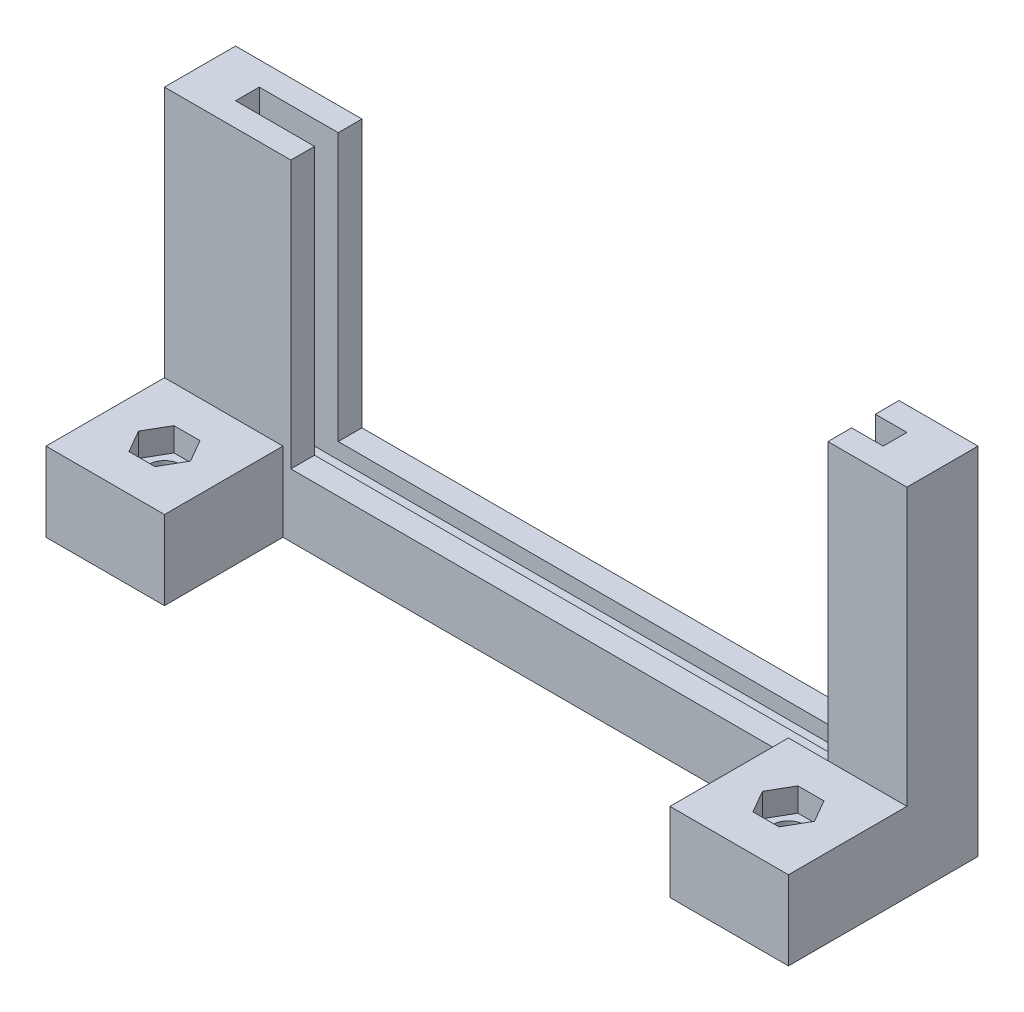
SolidWorks part; units mm, degrees
ref_plane "Plan de face" through (0, 0, 0) normal (0, 0, 1) x (1, 0, 0)
ref_plane "Plan de dessus" through (0, 0, 0) normal (0, 1, 0) x (1, 0, 0)
ref_plane "Plan de droite" through (0, 0, 0) normal (1, 0, 0) x (0, 0, -1)
sketch "Esquisse1" plane through (0, 0, 0) normal (0, 0, 1) x (1, 0, 0)
  line L17 (26.3064, -26.8419) -> (-41.6936, -26.8419)
  line L18 (26.3064, -26.8419) -> (26.3064, -34.8419) construction
  line L19 (26.3064, -34.8419) -> (-41.6936, -34.8419)
  line L20 (-41.6936, -26.8419) -> (-41.6936, -34.8419) construction
  line L21 (26.3064, 10.1581) -> (36.3064, 10.1581)
  line L22 (26.3064, 10.1581) -> (26.3064, -34.8419) construction
  line L23 (26.3064, -34.8419) -> (36.3064, -34.8419)
  line L24 (36.3064, 10.1581) -> (36.3064, -34.8419)
  line L26 (-41.6936, 7.0239) -> (-41.6936, -26.8419)
  line L27 (-41.6936, -34.8419) -> (-57.6936, -34.8419)
  line L28 (-41.6936, -34.8419) -> (-41.6936, 7.0239) construction
  line L29 (-41.6936, 7.0239) -> (-57.6936, 7.0239)
  line L30 (-57.6936, -34.8419) -> (-57.6936, 7.0239)
  line L31 (26.3064, 10.1581) -> (26.3064, -26.8419)
  dimension "D1" = 45
  dimension "D2" = 78
  dimension "D3" = 10
  dimension "D4" = 8
  dimension "D5" = 16
extrude "Boss.-Extru.1" add sketch "Esquisse1" along normal blind 3
sketch "Esquisse2" plane through (0, 0, 3) normal (0, 0, 1) x (1, 0, 0)
  line L0 (-57.6936, 7.0239) -> (-57.6936, -34.8419)
  line L1 (-57.6936, -34.8419) -> (36.3064, -34.8419)
  line L2 (36.3064, -34.8419) -> (36.3064, 10.1581)
  line L3 (36.3064, 10.1581) -> (30.3064, 10.1581)
  line L4 (36.3064, 10.1581) -> (26.3064, 10.1581) construction
  line L5 (30.3064, 10.1581) -> (30.3064, -28.8419)
  line L6 (30.3064, -28.8419) -> (-51.6936, -28.8419)
  line L7 (-51.6936, -28.8419) -> (-51.6936, 7.0239)
  line L8 (-41.6936, 7.0239) -> (-57.6936, 7.0239) construction
  line L9 (-51.6936, 7.0239) -> (-57.6936, 7.0239)
  dimension "D1" = 6
  dimension "D2" = 6
  dimension "D3" = 6
extrude "Boss.-Extru.2" add sketch "Esquisse2" along normal blind 1.5
ref_plane "Plan1" through (0, 0, 4.5) normal (0, 0, 1) x (1, 0, 0)
mirror "Symétrie3" about plane through (0, 0, 4.5) normal (0, 0, 1) of bodies 105
sketch "Esquisse3" plane through (0, -34.8419, 0) normal (0, -1, 0) x (1, 0, 0)
  line L1 (-57.6936, 9) -> (-42.6936, 9)
  line L2 (-57.6936, 9) -> (-57.6936, 24)
  line L3 (-57.6936, 24) -> (-42.6936, 24)
  line L4 (-42.6936, 9) -> (-42.6936, 24)
  line L5 (36.3064, 9) -> (21.3064, 9)
  line L6 (36.3064, 9) -> (36.3064, 24)
  line L7 (36.3064, 24) -> (21.3064, 24)
  line L8 (21.3064, 9) -> (21.3064, 24)
  dimension "D1" = 15
  dimension "D2" = 15
  dimension "D3" = 15
  dimension "D4" = 15
extrude "Boss.-Extru.3" add sketch "Esquisse3" against normal blind 10
sketch "Esquisse4" plane through (0, -24.8419, 0) normal (0, 1, 0) x (1, 0, 0)
  line L0 (-57.6936, -9) -> (-42.6936, -24) construction
  line L1 (36.3064, -9) -> (21.3064, -24) construction
  circle A0 centre (-50.1936, -16.5) radius 2
  circle A1 centre (28.8064, -16.5) radius 2
  dimension "D1" = 4
extrude "Enlèv. mat.-Extru.1" cut sketch "Esquisse4" against normal blind 10
sketch "Esquisse5" plane through (0, -24.8419, 0) normal (0, 1, 0) x (1, 0, 0)
  line L0 (-51.839, -13.65) -> (-48.5481, -13.65)
  line L1 (-48.5481, -13.65) -> (-46.9027, -16.5)
  line L3 (-48.5481, -19.35) -> (-51.839, -19.35)
  line L4 (-51.839, -19.35) -> (-53.4845, -16.5)
  line L5 (-53.4845, -16.5) -> (-51.839, -13.65)
  line L6 (-46.9027, -16.5) -> (-48.5481, -19.35)
  line L7 (-53.4845, -16.5) -> (-46.9027, -16.5) construction
  line L8 (27.161, -13.65) -> (30.4519, -13.65)
  line L9 (30.4519, -13.65) -> (32.0973, -16.5)
  line L10 (30.4519, -19.35) -> (27.161, -19.35)
  line L11 (27.161, -19.35) -> (25.5155, -16.5)
  line L12 (25.5155, -16.5) -> (27.161, -13.65)
  line L13 (32.0973, -16.5) -> (30.4519, -19.35)
  line L14 (25.5155, -16.5) -> (32.0973, -16.5) construction
  point P2 (-50.1936, -16.5)
  point P7 (-50.1936, -16.5)
  point P8 (28.8064, -16.5)
  point P11 (28.8064, -16.5)
  point P18 (0, 0)
  point P19 (0, 0)
  dimension "D1" = 5.7
  dimension "D2" = 120
  dimension "D3" = 5.7
  dimension "D4" = 120
extrude "Enlèv. mat.-Extru.2" cut sketch "Esquisse5" against normal blind 3
